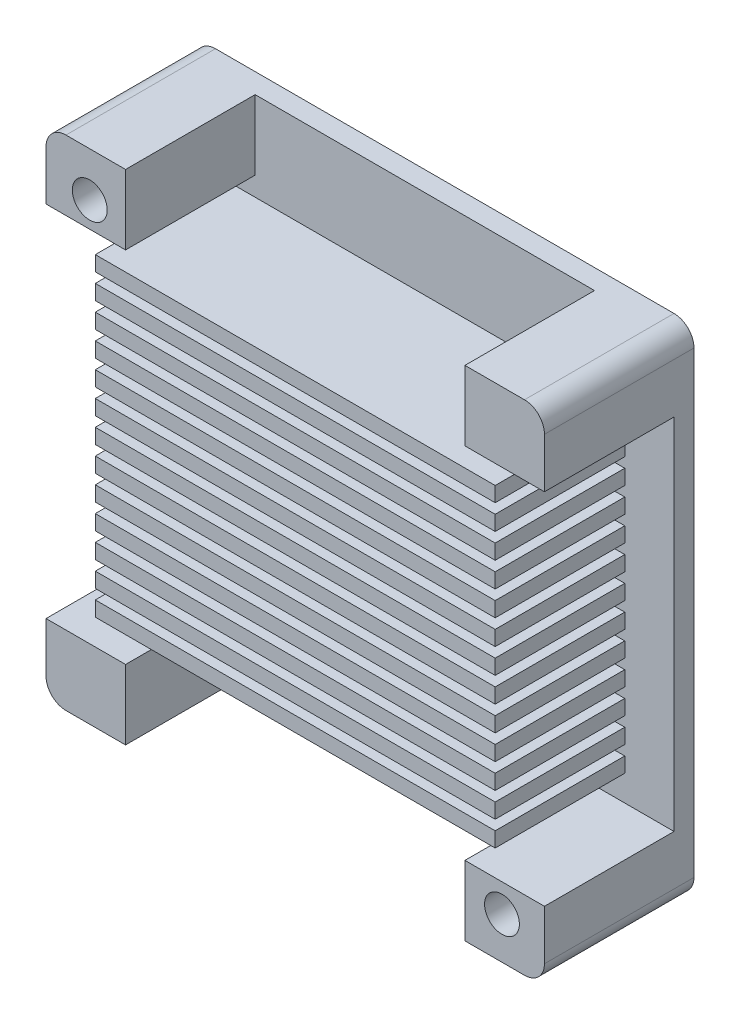
SolidWorks part; units mm, degrees
material "1.4000 (X6Cr13)"
ref_plane "Plan de face" through (0, 0, 0) normal (0, 0, 1) x (1, 0, 0)
ref_plane "Plan de dessus" through (0, 0, 0) normal (0, 1, 0) x (1, 0, 0)
ref_plane "Plan de droite" through (0, 0, 0) normal (1, 0, 0) x (0, 0, -1)
sketch "matrice" plane through (0, 0, 0) normal (0, 0, 1) x (1, 0, 0)
  line L0 (109.9513, -67.564) -> (89.5096, -67.564) construction
  line L2 (129.4892, -106.6064) -> (129.4892, -107.5436) construction
  line L3 (105.4414, -83.404) -> (113.4214, -91.384) construction
  line L4 (129.4892, -107.5436) -> (89.5096, -107.5436)
  line L5 (129.4892, -107.5436) -> (129.4892, -67.564)
  line L6 (129.4892, -67.564) -> (89.5096, -67.564)
  line L7 (89.5096, -107.5436) -> (89.5096, -67.564)
  line L8 (90.045, -68.0938) -> (88.817, -66.847) construction
  line L9 (105.429, -91.3964) -> (113.4338, -91.3964)
  line L10 (105.429, -91.3964) -> (105.429, -83.3916)
  line L11 (105.429, -83.3916) -> (113.4338, -83.3916)
  line L12 (113.4338, -91.3964) -> (113.4338, -83.3916)
  line L13 (105.429, -91.3964) -> (113.4338, -83.3916) construction
  line L14 (105.429, -83.3916) -> (113.4338, -91.3964) construction
  line L15 (128.9362, -106.985) -> (130.1704, -108.2197) construction
  line L17 (84.4314, -112.394) -> (134.4314, -112.394)
  line L18 (84.4314, -112.394) -> (84.4314, -62.394)
  line L19 (84.4314, -62.394) -> (134.4314, -62.394)
  line L20 (134.4314, -112.394) -> (134.4314, -62.394)
  line L21 (84.4314, -112.394) -> (134.4314, -62.394) construction
  line L22 (84.4314, -62.394) -> (134.4314, -112.394) construction
  circle A3 centre (130.1704, -108.2197) radius 1.7457
  circle A5 centre (88.817, -66.847) radius 1.75
  point P11 (109.4314, -87.394)
  point P31 (109.4314, -87.394)
  dimension "D2" = 50
  dimension "D1" = 50
sketch "bottomview" plane through (0, 0, 0) normal (0, 0, 1) x (1, 0, 0)
  line L1 (84.4314, -62.394) -> (134.4314, -62.394)
  line L2 (84.4314, -62.394) -> (84.4314, -112.394)
  line L3 (84.4314, -112.394) -> (134.4314, -112.394)
  line L4 (134.4314, -62.394) -> (134.4314, -112.394)
  circle A0 centre (88.817, -66.847) radius 1.75
  circle A1 centre (130.1704, -108.2197) radius 1.7457
extrude "Boss.-Extru.1" add sketch "bottomview" along normal blind 15
sketch "Esquisse4" plane through (0, 0, 0) normal (0, 0, -1) x (-1, 0, 0)
  line L0 (-109.4314, -87.394) -> (-109.4994, -107.5436) construction
  line L5 (-114.4314, -92.394) -> (-104.4314, -92.394)
  line L6 (-114.4314, -92.394) -> (-114.4314, -82.394)
  line L7 (-114.4314, -82.394) -> (-104.4314, -82.394)
  line L8 (-104.4314, -92.394) -> (-104.4314, -82.394)
  line L9 (-114.4314, -92.394) -> (-104.4314, -82.394) construction
  line L10 (-114.4314, -82.394) -> (-104.4314, -92.394) construction
  line L11 (-129.4892, -107.5436) -> (-89.5096, -107.5436) construction
  line L12 (-109.4314, -87.394) -> (-89.5096, -87.394) construction
  line L13 (-118.8871, -103.3592) -> (-100.0535, -103.3592)
  line L14 (-118.8871, -103.3592) -> (-118.8871, -94.4856)
  line L15 (-118.8871, -94.4856) -> (-100.0535, -94.4856)
  line L16 (-100.0535, -103.3592) -> (-100.0535, -94.4856)
  line L17 (-118.8871, -103.3592) -> (-100.0535, -94.4856) construction
  line L18 (-118.8871, -94.4856) -> (-100.0535, -103.3592) construction
  line L19 (-89.5096, -107.5436) -> (-89.5096, -67.564) construction
  line L20 (-118.8871, -71.4288) -> (-118.8871, -80.3024)
  line L21 (-118.8871, -71.4288) -> (-100.0535, -71.4288)
  line L22 (-100.0535, -71.4288) -> (-100.0535, -80.3024)
  line L23 (-118.8871, -80.3024) -> (-100.0535, -80.3024)
  circle A0 centre (-130.1704, -108.2197) radius 1.7457
  circle A1 centre (-130.1704, -108.2197) radius 3
  circle A2 centre (-88.817, -66.847) radius 1.75
  circle A3 centre (-88.817, -66.847) radius 3
  point P4 (-109.4703, -98.9224)
  point P6 (-109.4314, -87.394)
  dimension "D2" = 10
  dimension "D3" = 10
extrude "Boss.-Extru.2" add sketch "Esquisse4" along normal blind 1
fillet "Congé1" radius 1 4 edges at (114.4314, -92.394, -0.5) (104.4314, -92.394, -0.5) (114.4314, -82.394, -0.5) (104.4314, -82.394, -0.5)
fillet "Congé2" radius 1 8 edges at (118.8871, -94.4856, -0.5) (118.8871, -103.3592, -0.5) (100.0535, -103.3592, -0.5) (100.0535, -94.4856, -0.5) (100.0535, -80.3024, -0.5) (100.0535, -71.4288, -0.5) (118.8871, -80.3024, -0.5) (118.8871, -71.4288, -0.5)
sketch "fans" plane through (0, 0, 15) normal (0, 0, 1) x (1, 0, 0)
  line L0 (109.4314, -87.394) -> (109.4314, -72.0607) construction
  line L1 (129.4892, -107.5436) -> (129.4892, -67.564) construction
  line L2 (89.3736, -72.8107) -> (129.4892, -72.8107)
  line L3 (89.3736, -72.8107) -> (89.3736, -71.3107)
  line L4 (89.3736, -71.3107) -> (129.4892, -71.3107)
  line L5 (129.4892, -72.8107) -> (129.4892, -71.3107)
  line L6 (89.3736, -72.8107) -> (129.4892, -71.3107) construction
  line L7 (89.3736, -71.3107) -> (129.4892, -72.8107) construction
  line L8 (89.3736, -75.3107) -> (129.4892, -75.3107)
  line L9 (129.4892, -75.3107) -> (129.4892, -73.8107)
  line L10 (89.3736, -73.8107) -> (129.4892, -73.8107)
  line L11 (89.3736, -75.3107) -> (89.3736, -73.8107)
  line L12 (89.3736, -77.8107) -> (129.4892, -77.8107)
  line L13 (129.4892, -77.8107) -> (129.4892, -76.3107)
  line L14 (89.3736, -76.3107) -> (129.4892, -76.3107)
  line L15 (89.3736, -77.8107) -> (89.3736, -76.3107)
  line L16 (89.3736, -80.3107) -> (129.4892, -80.3107)
  line L17 (129.4892, -80.3107) -> (129.4892, -78.8107)
  line L18 (89.3736, -78.8107) -> (129.4892, -78.8107)
  line L19 (89.3736, -80.3107) -> (89.3736, -78.8107)
  line L20 (89.3736, -82.8107) -> (129.4892, -82.8107)
  line L21 (129.4892, -82.8107) -> (129.4892, -81.3107)
  line L22 (89.3736, -81.3107) -> (129.4892, -81.3107)
  line L23 (89.3736, -82.8107) -> (89.3736, -81.3107)
  line L24 (89.3736, -85.3107) -> (129.4892, -85.3107)
  line L25 (129.4892, -85.3107) -> (129.4892, -83.8107)
  line L26 (89.3736, -83.8107) -> (129.4892, -83.8107)
  line L27 (89.3736, -85.3107) -> (89.3736, -83.8107)
  line L28 (89.3736, -87.8107) -> (129.4892, -87.8107)
  line L29 (129.4892, -87.8107) -> (129.4892, -86.3107)
  line L30 (89.3736, -86.3107) -> (129.4892, -86.3107)
  line L31 (89.3736, -87.8107) -> (89.3736, -86.3107)
  line L32 (89.3736, -90.3107) -> (129.4892, -90.3107)
  line L33 (129.4892, -90.3107) -> (129.4892, -88.8107)
  line L34 (89.3736, -88.8107) -> (129.4892, -88.8107)
  line L35 (89.3736, -90.3107) -> (89.3736, -88.8107)
  line L36 (89.3736, -92.8107) -> (129.4892, -92.8107)
  line L37 (129.4892, -92.8107) -> (129.4892, -91.3107)
  line L38 (89.3736, -91.3107) -> (129.4892, -91.3107)
  line L39 (89.3736, -92.8107) -> (89.3736, -91.3107)
  line L40 (89.3736, -95.3107) -> (129.4892, -95.3107)
  line L41 (129.4892, -95.3107) -> (129.4892, -93.8107)
  line L42 (89.3736, -93.8107) -> (129.4892, -93.8107)
  line L43 (89.3736, -95.3107) -> (89.3736, -93.8107)
  line L44 (89.3736, -97.8107) -> (129.4892, -97.8107)
  line L45 (129.4892, -97.8107) -> (129.4892, -96.3107)
  line L46 (89.3736, -96.3107) -> (129.4892, -96.3107)
  line L47 (89.3736, -97.8107) -> (89.3736, -96.3107)
  line L48 (89.3736, -100.3107) -> (129.4892, -100.3107)
  line L49 (129.4892, -100.3107) -> (129.4892, -98.8107)
  line L50 (89.3736, -98.8107) -> (129.4892, -98.8107)
  line L51 (89.3736, -100.3107) -> (89.3736, -98.8107)
  line L52 (89.3736, -102.8107) -> (129.4892, -102.8107)
  line L53 (129.4892, -102.8107) -> (129.4892, -101.3107)
  line L54 (89.3736, -101.3107) -> (129.4892, -101.3107)
  line L55 (89.3736, -102.8107) -> (89.3736, -101.3107)
  line L56 (134.4314, -112.394) -> (134.4314, -62.394) construction
  line L57 (84.4314, -105.3996) -> (134.4314, -105.3996)
  line L58 (84.4314, -105.3996) -> (84.4314, -69.3884)
  line L59 (84.4314, -69.3884) -> (134.4314, -69.3884)
  line L60 (134.4314, -105.3996) -> (134.4314, -69.3884)
  line L61 (84.4314, -105.3996) -> (134.4314, -69.3884) construction
  line L62 (84.4314, -69.3884) -> (134.4314, -105.3996) construction
  dimension "D1" = 1.5
  dimension "D2" = 13
extrude "Enlèv. mat.-Extru.1" cut sketch "fans" against normal blind 13
sketch "Esquisse6" plane through (0, 0, 15) normal (0, 0, 1) x (1, 0, 0)
  line L0 (109.4314, -62.394) -> (109.4314, -69.3884) construction
  line L1 (84.4314, -62.394) -> (134.4314, -62.394) construction
  line L2 (134.4314, -69.3884) -> (84.4314, -69.3884) construction
  line L3 (109.4314, -87.394) -> (136.0599, -87.394) construction
  line L4 (92.4091, -69.3884) -> (126.4537, -69.3884)
  line L5 (92.4091, -69.3884) -> (92.4091, -62.394)
  line L6 (92.4091, -62.394) -> (126.4537, -62.394)
  line L7 (126.4537, -69.3884) -> (126.4537, -62.394)
  line L8 (92.4091, -69.3884) -> (126.4537, -62.394) construction
  line L9 (92.4091, -62.394) -> (126.4537, -69.3884) construction
  line L10 (92.4091, -105.3996) -> (92.4091, -112.394)
  line L11 (92.4091, -112.394) -> (126.4537, -112.394)
  line L12 (126.4537, -105.3996) -> (126.4537, -112.394)
  line L13 (92.4091, -105.3996) -> (126.4537, -105.3996)
  point P6 (109.4314, -65.8912)
extrude "Enlèv. mat.-Extru.2" cut sketch "Esquisse6" against normal blind 13
fillet "Congé3" radius 2 4 edges at (84.4314, -62.394, 7.5) (134.4314, -62.394, 7.5) (134.4314, -112.394, 7.5) (84.4314, -112.394, 7.5)
sketch "Esquisse7" plane through (0, 0, 0) normal (0, 0, -1) x (-1, 0, 0)
  line L0 (-100.0535, -75.8656) -> (-118.8871, -75.8656) construction
  line L1 (-105.429, -91.3964) -> (-113.4338, -91.3964)
  line L2 (-105.429, -91.3964) -> (-105.429, -83.3916)
  line L3 (-105.429, -83.3916) -> (-113.4338, -83.3916)
  line L4 (-113.4338, -91.3964) -> (-113.4338, -83.3916)
  line L5 (-105.429, -91.3964) -> (-113.4338, -83.3916) construction
  line L6 (-105.429, -83.3916) -> (-113.4338, -91.3964) construction
  line L7 (-100.0535, -79.3024) -> (-100.0535, -72.4288) construction
  line L8 (-118.8871, -72.4288) -> (-118.8871, -79.3024) construction
  line L9 (-109.4314, -87.394) -> (-99.5695, -87.394) construction
  line L10 (-118.0041, -71.3016) -> (-100.9365, -71.3016)
  line L11 (-119.0041, -72.3016) -> (-119.0041, -79.4296)
  line L12 (-118.0041, -80.4296) -> (-100.9365, -80.4296)
  line L13 (-99.9365, -72.3016) -> (-99.9365, -79.4296)
  line L14 (-119.0041, -71.3016) -> (-99.9365, -80.4296) construction
  line L15 (-119.0041, -80.4296) -> (-99.9365, -71.3016) construction
  line L16 (-118.0041, -103.4864) -> (-100.9365, -103.4864)
  line L17 (-119.0041, -102.4864) -> (-119.0041, -95.3584)
  line L18 (-118.0041, -94.3584) -> (-100.9365, -94.3584)
  line L19 (-99.9365, -102.4864) -> (-99.9365, -95.3584)
  line L20 (-129.4892, -107.5436) -> (-89.5096, -107.5436) construction
  line L21 (-122.0905, -67.2444) -> (-98.0635, -67.2444)
  line L22 (-123.0905, -68.2444) -> (-123.0905, -101.6932)
  line L23 (-110.7497, -107.5436) -> (-96.7723, -107.5436)
  line L24 (-95.7723, -72.3107) -> (-95.7723, -106.5436)
  line L25 (-123.0905, -67.2444) -> (-95.7723, -107.5436) construction
  line L26 (-123.0905, -107.5436) -> (-95.7723, -67.2444) construction
  line L27 (-111.7497, -108.5436) -> (-111.7497, -111.394)
  line L32 (-111.7497, -102.6932) -> (-134.4314, -112.394) construction
  line L33 (-111.7497, -112.394) -> (-134.4314, -102.6932) construction
  line L34 (-124.0905, -102.6932) -> (-133.4314, -102.6932)
  line L35 (-134.4314, -103.6932) -> (-134.4314, -110.394)
  line L36 (-86.4314, -62.394) -> (-94.7723, -62.394)
  line L37 (-84.4314, -64.394) -> (-84.4314, -70.3107)
  line L38 (-85.4314, -71.3107) -> (-94.7723, -71.3107)
  line L40 (-98.0635, -67.2444) -> (-96.7723, -67.2444)
  line L45 (-95.7723, -63.394) -> (-95.7723, -66.2444)
  line L46 (-132.4314, -112.394) -> (-112.7497, -112.394)
  arc A0 (-119.0041, -79.4296) -> (-118.0041, -80.4296) centre (-118.0041, -79.4296) ccw
  arc A1 (-118.0041, -71.3016) -> (-119.0041, -72.3016) centre (-118.0041, -72.3016) ccw
  arc A2 (-100.9365, -71.3016) -> (-99.9365, -72.3016) centre (-100.9365, -72.3016) cw
  arc A3 (-100.9365, -80.4296) -> (-99.9365, -79.4296) centre (-100.9365, -79.4296) ccw
  arc A4 (-100.9365, -103.4864) -> (-99.9365, -102.4864) centre (-100.9365, -102.4864) ccw
  arc A5 (-118.0041, -103.4864) -> (-119.0041, -102.4864) centre (-118.0041, -102.4864) cw
  arc A6 (-119.0041, -95.3584) -> (-118.0041, -94.3584) centre (-118.0041, -95.3584) cw
  arc A7 (-100.9365, -94.3584) -> (-99.9365, -95.3584) centre (-100.9365, -95.3584) cw
  circle A8 centre (-130.1704, -108.2197) radius 1.7457
  arc A9 (-111.7497, -108.5436) -> (-110.7497, -107.5436) centre (-110.7497, -108.5436) cw
  arc A10 (-111.7497, -111.394) -> (-112.7497, -112.394) centre (-112.7497, -111.394) cw
  arc A11 (-124.0905, -102.6932) -> (-123.0905, -101.6932) centre (-124.0905, -101.6932) ccw
  arc A12 (-133.4314, -102.6932) -> (-134.4314, -103.6932) centre (-133.4314, -103.6932) ccw
  arc A14 (-122.0905, -67.2444) -> (-123.0905, -68.2444) centre (-122.0905, -68.2444) ccw
  arc A15 (-96.7723, -107.5436) -> (-95.7723, -106.5436) centre (-96.7723, -106.5436) ccw
  arc A16 (-95.7723, -72.3107) -> (-94.7723, -71.3107) centre (-94.7723, -72.3107) cw
  arc A17 (-84.4314, -70.3107) -> (-85.4314, -71.3107) centre (-85.4314, -70.3107) cw
  arc A18 (-95.7723, -66.2444) -> (-96.7723, -67.2444) centre (-96.7723, -66.2444) cw
  arc A19 (-94.7723, -62.394) -> (-95.7723, -63.394) centre (-94.7723, -63.394) ccw
  arc A20 (-86.4314, -62.394) -> (-84.4314, -64.394) centre (-86.4314, -64.394) cw
  arc A21 (-134.4314, -110.394) -> (-132.4314, -112.394) centre (-132.4314, -110.394) ccw
  circle A22 centre (-88.817, -66.847) radius 1.75
  point P0 (-109.4314, -87.394)
  point P13 (-109.4703, -75.8656)
  point P96 (-84.4314, -62.394)
  dimension "D1" = 1
  dimension "D2" = 1
  dimension "D3" = 1
  dimension "D4" = 2
  dimension "D5" = 2
sketch "Esquisse8" plane through (0, 0, -1) normal (0, 0, -1) x (-1, 0, 0)
  line L0 (-117.8871, -71.4288) -> (-101.0535, -71.4288)
  line L1 (-100.0535, -72.4288) -> (-100.0535, -79.3024)
  line L2 (-101.0535, -80.3024) -> (-117.8871, -80.3024)
  line L3 (-118.8871, -79.3024) -> (-118.8871, -72.4288)
  line L4 (-109.4314, -87.394) -> (-104.7022, -87.394) construction
  line L5 (-109.4314, -87.394) -> (-99.5695, -87.394) construction
  line L6 (-100.0535, -102.3592) -> (-100.0535, -95.4856)
  line L7 (-117.8871, -103.3592) -> (-101.0535, -103.3592)
  line L8 (-118.8871, -95.4856) -> (-118.8871, -102.3592)
  line L9 (-101.0535, -94.4856) -> (-117.8871, -94.4856)
  arc A0 (-118.8871, -72.4288) -> (-117.8871, -71.4288) centre (-117.8871, -72.4288) cw
  arc A1 (-101.0535, -71.4288) -> (-100.0535, -72.4288) centre (-101.0535, -72.4288) cw
  arc A2 (-100.0535, -79.3024) -> (-101.0535, -80.3024) centre (-101.0535, -79.3024) cw
  arc A3 (-117.8871, -80.3024) -> (-118.8871, -79.3024) centre (-117.8871, -79.3024) cw
  arc A4 (-100.0535, -95.4856) -> (-101.0535, -94.4856) centre (-101.0535, -95.4856) ccw
  arc A5 (-101.0535, -103.3592) -> (-100.0535, -102.3592) centre (-101.0535, -102.3592) ccw
  arc A6 (-118.8871, -102.3592) -> (-117.8871, -103.3592) centre (-117.8871, -102.3592) ccw
  arc A7 (-117.8871, -94.4856) -> (-118.8871, -95.4856) centre (-117.8871, -95.4856) ccw
extrude "Boss.-Extru.3" add sketch "Esquisse8" along normal up to surface (1 mm away)
